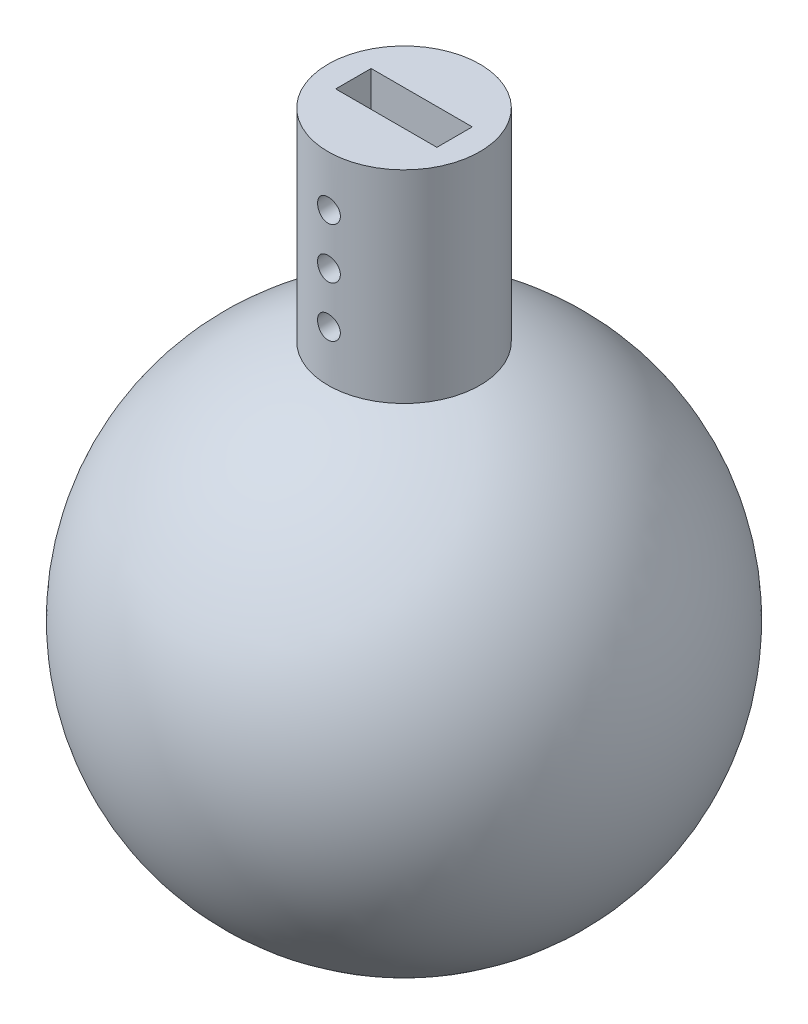
SolidWorks part; units mm, degrees
material "Rubber"
ref_plane "Front Plane" through (0, 0, 0) normal (0, 0, 1) x (1, 0, 0)
ref_plane "Top Plane" through (0, 0, 0) normal (0, 1, 0) x (1, 0, 0)
ref_plane "Right Plane" through (0, 0, 0) normal (1, 0, 0) x (0, 0, -1)
sketch "Sketch1" plane through (0, 0, 0) normal (0, 0, 1) x (1, 0, 0)
  line L0 (0, 0) -> (0, 40)
  line L1 (0, 40) -> (15, 40)
  line L2 (15, 40) -> (15, -47.697)
  line L3 (15, -47.697) -> (15, -97.697)
  arc A0 (0, 0) -> (15, -97.697) centre (15, -47.697) ccw
  dimension "D3" = 50
  dimension "D1" = 40
  dimension "D2" = 15
revolve "Revolve1" add sketch "Sketch1" angle 360 about L2
sketch "Sketch2" plane through (0, 0, 0) normal (0, 0, 1) x (1, 0, 0)
  line L0 (30, 40) -> (0, 40) construction
  line L1 (30, 0) -> (30, 40) construction
  circle A0 centre (15, 30) radius 2.25
  circle A1 centre (15, 20) radius 2.25
  circle A2 centre (15, 10) radius 2.25
  dimension "D1" = 4.5
  dimension "D2" = 10
  dimension "D3" = 15
  dimension "D4" = 3
extrude "Cut-Extrude1" cut sketch "Sketch2" against normal blind 15 and the other way blind 15
sketch "Sketch3" plane through (0, 40, 0) normal (0, 1, 0) x (1, 0, 0)
  line L1 (5, -3.5) -> (25, -3.5)
  line L2 (5, -3.5) -> (5, 3.5)
  line L3 (5, 3.5) -> (25, 3.5)
  line L4 (25, -3.5) -> (25, 3.5)
  line L5 (5, -3.5) -> (25, 3.5) construction
  line L6 (5, 3.5) -> (25, -3.5) construction
  point P0 (15, 0)
  dimension "D1" = 20
  dimension "D2" = 7
extrude "Cut-Extrude2" cut sketch "Sketch3" against normal blind 40
